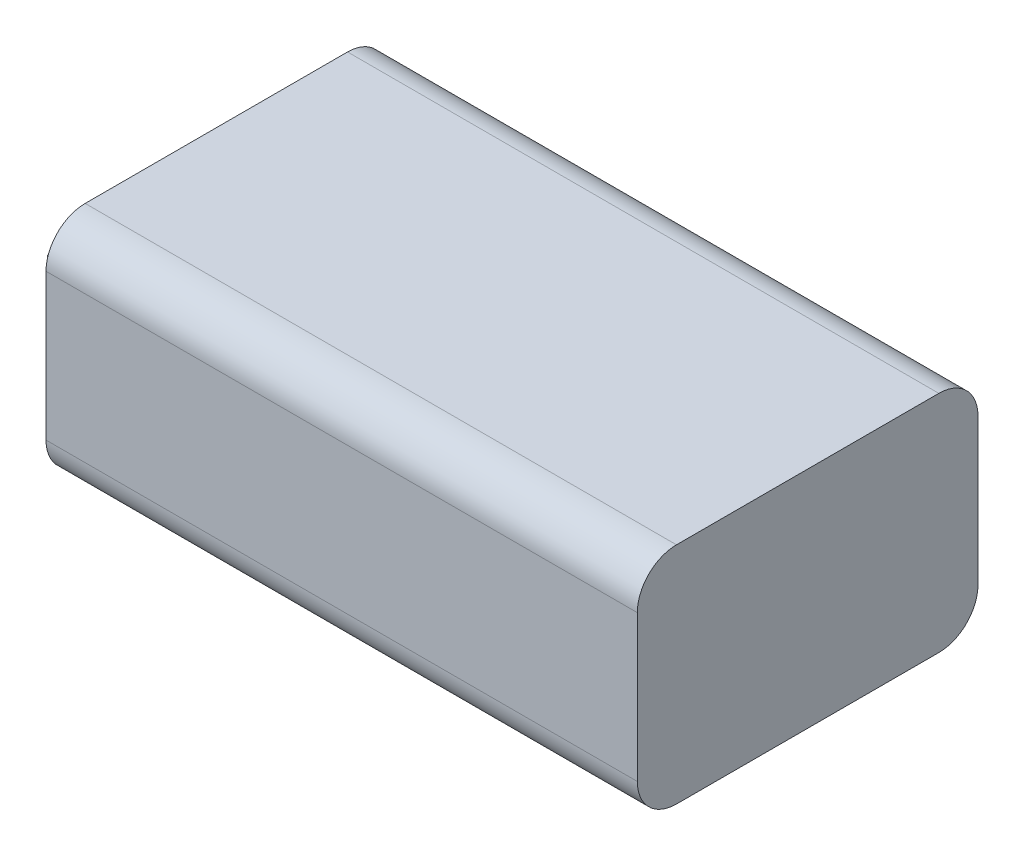
SolidWorks part; units mm, degrees
ref_plane "Front Plane" through (0, 0, 0) normal (0, 0, 1) x (1, 0, 0)
ref_plane "Top Plane" through (0, 0, 0) normal (0, 1, 0) x (1, 0, 0)
ref_plane "Right Plane" through (0, 0, 0) normal (1, 0, 0) x (0, 0, -1)
sketch "Sketch1" plane through (0, 0, 0) normal (0, 1, 0) x (1, 0, 0)
  line L1 (-32.2061, -9.8259) -> (13.0939, -9.8259)
  line L2 (-32.2061, -9.8259) -> (-32.2061, 16.2741)
  line L3 (-32.2061, 16.2741) -> (13.0939, 16.2741)
  line L4 (13.0939, -9.8259) -> (13.0939, 16.2741)
  line L5 (-32.2061, -7.0259) -> (-34.9061, -7.0259)
  line L6 (-32.2061, -7.0259) -> (-32.2061, 12.4741)
  line L7 (-32.2061, 12.4741) -> (-34.9061, 12.4741)
  line L8 (-34.9061, -7.0259) -> (-34.9061, 12.4741)
  dimension "D1" = 26.1
  dimension "D2" = 45.3
  dimension "D3" = 48
  dimension "D4" = 19.5
  dimension "D5" = 2.8
extrude "Boss-Extrude1" add sketch "Sketch1" along normal blind 17.2 contours L1 L4 L3 L2 region at (-9.5561, 0, -3.2241)
fillet "Fillet1" radius 3 4 edges at (-9.5561, 17.2, -16.2741) (-9.5561, 0, -16.2741) (-9.5561, 0, 9.8259) (-9.5561, 17.2, 9.8259)
extrude "Boss-Extrude2" add sketch "Sketch1<3>" along normal blind 8.5 from offset 4 contours L8 L5 L2 L7 region at (-33.5561, 0, -2.7241)
sketch "Sketch1<3>" plane through (0, 0, 0) normal (0, 1, 0) x (1, 0, 0) same geometry as "Sketch1"
